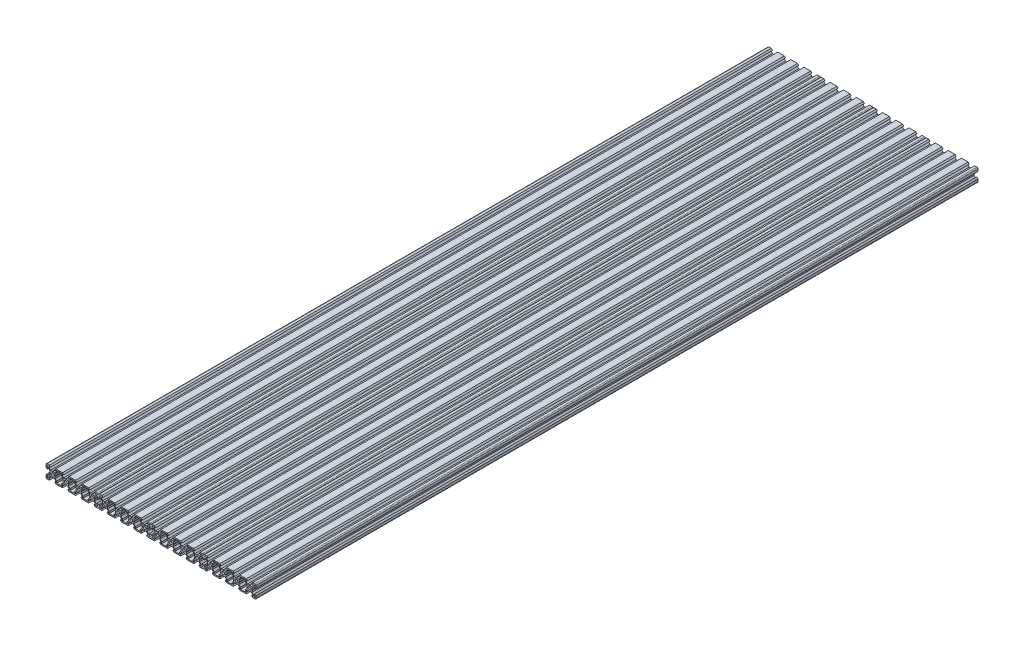
SolidWorks part; units mm, degrees
ref_plane "Front Plane" through (0, 0, 0) normal (0, 0, 1) x (1, 0, 0)
ref_plane "Top Plane" through (0, 0, 0) normal (0, 1, 0) x (1, 0, 0)
ref_plane "Right Plane" through (0, 0, 0) normal (1, 0, 0) x (0, 0, -1)
sketch "Sketch1" plane through (0, 0, 0) normal (0, 0, 1) x (1, 0, 0)
  line L0 (4.9, -10) -> (15.0977, -10)
  line L1 (-8.2011, 3.1) -> (-10.0011, 4.9)
  line L2 (-3.1, 8.2) -> (-5.4, 8.2)
  line L3 (-5.4, 8.2) -> (-5.4, 6.3)
  line L4 (-5.4, 6.3) -> (-3.1, 4)
  line L5 (-3.1, 4) -> (-0.5, 4)
  line L6 (3.1, 4) -> (5.4, 6.3)
  line L7 (5.4, 6.3) -> (5.4, 8.2)
  line L8 (5.4, 8.2) -> (3.1, 8.2)
  line L9 (-8.2135, -3.1) -> (-10.0011, -4.8876)
  line L10 (4.9, 10) -> (15.0977, 10)
  line L11 (0.5, 4) -> (3.1, 4)
  line L12 (5.4, -8.2) -> (3.1, -8.2)
  line L13 (5.4, -6.3) -> (5.4, -8.2)
  line L14 (3.1, -4) -> (5.4, -6.3)
  line L15 (-3.1, -4) -> (-0.5, -4)
  line L16 (-5.4, -6.3) -> (-3.1, -4)
  line L17 (-5.4, -8.2) -> (-5.4, -6.3)
  line L18 (-3.1, -8.2) -> (-5.4, -8.2)
  line L19 (-4.0135, 0.5) -> (-4.0135, 3.1)
  line L20 (-10.0011, -4.8876) -> (-10.0011, -8.5)
  line L21 (0.5, -4) -> (3.1, -4)
  line L22 (-8.2135, -3.1) -> (-8.2135, -5.4)
  line L23 (-8.2135, -5.4) -> (-6.3135, -5.4)
  line L24 (-6.3135, -5.4) -> (-4.0135, -3.1)
  line L25 (-4.0135, -3.1) -> (-4.0135, -0.5)
  line L26 (-4.0135, 3.1) -> (-6.3135, 5.4)
  line L27 (-6.3135, 5.4) -> (-8.2135, 5.4)
  line L28 (-8.2135, 5.4) -> (-8.2011, 3.1)
  line L29 (3.9989, 0.5) -> (3.9989, 3.1)
  line L30 (6.2989, 5.4) -> (6.2989, 8.2)
  line L31 (6.2989, -5.4) -> (6.2989, -8.2)
  line L32 (6.2989, -8.2) -> (13.6989, -8.2)
  line L33 (3.9989, 3.1) -> (6.2989, 5.4)
  line L34 (3.9989, -3.1) -> (3.9989, -0.5)
  line L35 (6.2989, -5.4) -> (3.9989, -3.1)
  line L36 (13.6989, -5.4) -> (13.6989, -8.2)
  line L37 (24.8977, 10) -> (35.1, 10)
  line L38 (24.8977, -10) -> (35.1, -10)
  line L39 (26.3113, -5.4) -> (26.3113, -8.2)
  line L40 (-10.0011, 8.5) -> (-10.0011, 4.9)
  line L41 (-8.5011, 10) -> (-4.9, 10)
  line L42 (-10.0011, 8.5) -> (-10.0011, 4.9)
  line L43 (-8.5011, -10) -> (-4.9, -10)
  line L44 (6.2989, 8.2) -> (13.6989, 8.2)
  line L45 (-8.2011, 7.0732) -> (-8.2011, 7.7)
  line L46 (-7.7011, 8.2) -> (-7.0738, 8.2)
  line L47 (-6.8971, 7.7732) -> (-7.7744, 6.8964)
  line L48 (-3.1, 8.2) -> (-4.9, 10)
  line L49 (3.1, 8.2) -> (4.9, 10)
  line L50 (-3.1, -8.2) -> (-4.9, -10)
  line L51 (3.1, -8.2) -> (4.9, -10)
  line L52 (36.9, 8.2) -> (34.6, 8.2)
  line L53 (34.6, 8.2) -> (34.6, 6.3)
  line L54 (13.6989, 8.2) -> (13.6989, 5.4)
  line L55 (34.6, 6.3) -> (36.9, 4)
  line L56 (36.9, 4) -> (39.5, 4)
  line L57 (43.1, 4) -> (45.4, 6.3)
  line L58 (45.4, 6.3) -> (45.4, 8.2)
  line L59 (45.4, 8.2) -> (43.1, 8.2)
  line L60 (-6.8971, -7.7732) -> (-7.7744, -6.8964)
  line L61 (-7.7011, -8.2) -> (-7.0738, -8.2)
  line L62 (-8.2011, -7.0732) -> (-8.2011, -7.7)
  line L63 (26.3113, -8.2) -> (33.6865, -8.2)
  line L64 (33.6865, -8.2) -> (33.6865, -5.4)
  line L65 (26.3113, 5.4) -> (26.3113, 8.2)
  line L66 (40.5, 4) -> (43.1, 4)
  line L67 (45.4, -8.2) -> (43.1, -8.2)
  line L68 (45.4, -6.3) -> (45.4, -8.2)
  line L69 (43.1, -4) -> (45.4, -6.3)
  line L70 (36.9, -4) -> (39.5, -4)
  line L71 (34.6, -6.3) -> (36.9, -4)
  line L72 (34.6, -8.2) -> (34.6, -6.3)
  line L73 (16.8977, -8.2) -> (15.0977, -10)
  line L74 (23.0977, -8.2) -> (24.8977, -10)
  line L75 (16.8977, 8.2) -> (15.0977, 10)
  line L76 (23.0977, 8.2) -> (24.8977, 10)
  line L77 (26.3113, 8.2) -> (33.6865, 8.2)
  line L78 (33.6865, 8.2) -> (33.6865, 5.4)
  line L84 (36.9, -8.2) -> (34.6, -8.2)
  line L85 (35.9865, 0.5) -> (35.9865, 3.1)
  line L86 (40.5, -4) -> (43.1, -4)
  line L87 (13.6989, -5.4) -> (15.9989, -3.1)
  line L88 (15.9989, -3.1) -> (15.9989, -0.5)
  line L89 (15.9989, 3.1) -> (13.6989, 5.4)
  line L92 (15.9989, 0.5) -> (15.9989, 3.1)
  line L95 (24.0113, 3.1) -> (26.3113, 5.4)
  line L96 (24.0113, -3.1) -> (24.0113, -0.5)
  line L97 (26.3113, -5.4) -> (24.0113, -3.1)
  line L100 (19.4977, -4) -> (16.8977, -4)
  line L102 (24.0113, 0.5) -> (24.0113, 3.1)
  line L103 (23.0977, -8.2) -> (25.3977, -8.2)
  line L104 (25.3977, -8.2) -> (25.3977, -6.3)
  line L105 (25.3977, -6.3) -> (23.0977, -4)
  line L106 (23.0977, -4) -> (20.4977, -4)
  line L107 (16.8977, -4) -> (14.5977, -6.3)
  line L108 (14.5977, -6.3) -> (14.5977, -8.2)
  line L109 (14.5977, -8.2) -> (16.8977, -8.2)
  line L110 (19.4977, 4) -> (16.8977, 4)
  line L111 (33.6865, -5.4) -> (35.9865, -3.1)
  line L113 (14.5977, 8.2) -> (16.8977, 8.2)
  line L114 (14.5977, 6.3) -> (14.5977, 8.2)
  line L115 (16.8977, 4) -> (14.5977, 6.3)
  line L116 (23.0977, 4) -> (20.4977, 4)
  line L117 (25.3977, 6.3) -> (23.0977, 4)
  line L118 (25.3977, 8.2) -> (25.3977, 6.3)
  line L119 (23.0977, 8.2) -> (25.3977, 8.2)
  line L121 (35.9865, -3.1) -> (35.9865, -0.5)
  line L122 (35.9865, 3.1) -> (33.6865, 5.4)
  line L125 (43.9989, 0.5) -> (43.9989, 3.1)
  line L126 (43.9989, 3.1) -> (46.2989, 5.4)
  line L127 (43.9989, -3.1) -> (43.9989, -0.5)
  line L128 (46.2989, -5.4) -> (43.9989, -3.1)
  line L134 (36.9, 8.2) -> (35.1, 10)
  line L135 (43.1, 8.2) -> (44.9, 10)
  line L136 (36.9, -8.2) -> (35.1, -10)
  line L137 (43.1, -8.2) -> (44.9, -10)
  line L140 (68.1989, -7.0732) -> (68.1989, -7.7)
  line L141 (67.6989, -8.2) -> (67.0716, -8.2)
  line L142 (66.8948, -7.7732) -> (67.7721, -6.8964)
  line L143 (46.2989, 8.2) -> (46.2989, 5.4)
  line L144 (56.8977, -8.2) -> (55.0977, -10)
  line L145 (63.0977, -8.2) -> (64.8977, -10)
  line L146 (56.8977, 8.2) -> (55.0977, 10)
  line L147 (63.0977, 8.2) -> (64.8977, 10)
  line L148 (66.8948, 7.7732) -> (67.7721, 6.8964)
  line L149 (67.6989, 8.2) -> (67.0716, 8.2)
  line L150 (68.1989, 7.0732) -> (68.1989, 7.7)
  line L151 (53.6989, 8.2) -> (46.2989, 8.2)
  line L152 (68.4989, -10) -> (64.8977, -10)
  line L153 (69.9989, 8.5) -> (69.9989, 4.9)
  line L154 (68.4989, 10) -> (64.8977, 10)
  line L155 (69.9989, 8.5) -> (69.9989, 4.9)
  line L157 (46.2989, -5.4) -> (46.2989, -8.2)
  line L158 (53.6989, -5.4) -> (55.9989, -3.1)
  line L159 (55.9989, -3.1) -> (55.9989, -0.5)
  line L160 (55.9989, 3.1) -> (53.6989, 5.4)
  line L161 (53.6989, -8.2) -> (46.2989, -8.2)
  line L162 (53.6989, -5.4) -> (53.6989, -8.2)
  line L163 (53.6989, 5.4) -> (53.6989, 8.2)
  line L164 (55.9989, 0.5) -> (55.9989, 3.1)
  line L165 (68.2113, 5.4) -> (68.1989, 3.1)
  line L166 (66.3113, 5.4) -> (68.2113, 5.4)
  line L167 (64.0113, 3.1) -> (66.3113, 5.4)
  line L168 (64.0113, -3.1) -> (64.0113, -0.5)
  line L169 (66.3113, -5.4) -> (64.0113, -3.1)
  line L170 (68.2113, -5.4) -> (66.3113, -5.4)
  line L171 (68.2113, -3.1) -> (68.2113, -5.4)
  line L172 (59.4977, -4) -> (56.8977, -4)
  line L173 (69.9989, -4.8876) -> (69.9989, -8.5)
  line L174 (64.0113, 0.5) -> (64.0113, 3.1)
  line L175 (63.0977, -8.2) -> (65.3977, -8.2)
  line L176 (65.3977, -8.2) -> (65.3977, -6.3)
  line L177 (65.3977, -6.3) -> (63.0977, -4)
  line L178 (63.0977, -4) -> (60.4977, -4)
  line L179 (56.8977, -4) -> (54.5977, -6.3)
  line L180 (54.5977, -6.3) -> (54.5977, -8.2)
  line L181 (54.5977, -8.2) -> (56.8977, -8.2)
  line L182 (59.4977, 4) -> (56.8977, 4)
  line L183 (55.0977, 10) -> (44.9, 10)
  line L184 (68.2113, -3.1) -> (69.9989, -4.8876)
  line L185 (54.5977, 8.2) -> (56.8977, 8.2)
  line L186 (54.5977, 6.3) -> (54.5977, 8.2)
  line L187 (56.8977, 4) -> (54.5977, 6.3)
  line L188 (63.0977, 4) -> (60.4977, 4)
  line L189 (65.3977, 6.3) -> (63.0977, 4)
  line L190 (65.3977, 8.2) -> (65.3977, 6.3)
  line L191 (63.0977, 8.2) -> (65.3977, 8.2)
  line L192 (68.1989, 3.1) -> (69.9989, 4.9)
  line L193 (55.0977, -10) -> (44.9, -10)
  circle A0 centre (0, 0) radius 2.1
  arc A1 (-10.0011, -8.5) -> (-8.5011, -10) centre (-8.5011, -8.5) ccw
  arc A2 (0.5, -4) -> (-0.5, -4) centre (0, -4) ccw
  arc A3 (20.4977, -4) -> (19.4977, -4) centre (19.9977, -4) ccw
  arc A4 (-8.5011, 10) -> (-10.0011, 8.5) centre (-8.5011, 8.5) ccw
  arc A5 (-8.2011, 7.7) -> (-7.7011, 8.2) centre (-7.7011, 7.7) cw
  arc A6 (-7.0738, 8.2) -> (-6.8971, 7.7732) centre (-7.0738, 7.95) cw
  arc A7 (-8.2011, 7.0732) -> (-7.7744, 6.8964) centre (-7.9511, 7.0732) ccw
  arc A8 (-0.5, 4) -> (0.5, 4) centre (0, 4) ccw
  circle A9 centre (40, 0) radius 2.1
  arc A10 (-4.0135, -0.5) -> (-4.0135, 0.5) centre (-4.0135, 0) ccw
  arc A11 (3.9989, 0.5) -> (3.9989, -0.5) centre (3.9989, 0) ccw
  arc A17 (39.5, 4) -> (40.5, 4) centre (40, 4) ccw
  arc A18 (-8.2011, -7.0732) -> (-7.7744, -6.8964) centre (-7.9511, -7.0732) cw
  arc A19 (-7.0738, -8.2) -> (-6.8971, -7.7732) centre (-7.0738, -7.95) ccw
  arc A20 (-8.2011, -7.7) -> (-7.7011, -8.2) centre (-7.7011, -7.7) ccw
  arc A24 (35.9865, -0.5) -> (35.9865, 0.5) centre (35.9865, 0) ccw
  arc A25 (43.9989, 0.5) -> (43.9989, -0.5) centre (43.9989, 0) ccw
  arc A29 (68.1989, -7.7) -> (67.6989, -8.2) centre (67.6989, -7.7) cw
  arc A30 (15.9989, 0.5) -> (15.9989, -0.5) centre (15.9989, 0) cw
  arc A31 (24.0113, -0.5) -> (24.0113, 0.5) centre (24.0113, 0) cw
  arc A32 (67.0716, -8.2) -> (66.8948, -7.7732) centre (67.0716, -7.95) cw
  arc A33 (20.4977, 4) -> (19.4977, 4) centre (19.9977, 4) cw
  arc A38 (68.1989, -7.0732) -> (67.7721, -6.8964) centre (67.9489, -7.0732) ccw
  arc A39 (55.9989, 0.5) -> (55.9989, -0.5) centre (55.9989, 0) cw
  circle A41 centre (19.9977, 0) radius 2.1
  arc A42 (64.0113, -0.5) -> (64.0113, 0.5) centre (64.0113, 0) cw
  arc A43 (60.4977, 4) -> (59.4977, 4) centre (59.9977, 4) cw
  arc A44 (68.1989, 7.0732) -> (67.7721, 6.8964) centre (67.9489, 7.0732) cw
  arc A45 (67.0716, 8.2) -> (66.8948, 7.7732) centre (67.0716, 7.95) ccw
  arc A46 (68.1989, 7.7) -> (67.6989, 8.2) centre (67.6989, 7.7) ccw
  arc A47 (68.4989, 10) -> (69.9989, 8.5) centre (68.4989, 8.5) cw
  arc A48 (39.5, -4) -> (40.5, -4) centre (40, -4) cw
  arc A49 (59.4977, -4) -> (60.4977, -4) centre (59.9977, -4) cw
  arc A50 (69.9989, -8.5) -> (68.4989, -10) centre (68.4989, -8.5) cw
  circle A51 centre (59.9977, 0) radius 2.1
extrude "Boss-Extrude1" add sketch "Sketch1" along normal blind 1100 contours A50 L173 L184 L171 L170 L169 L168 A42 L174 L167 L166 L165 L192 L153 A47 L154 L147 L191 L190 L189 L188 A43 L182 L187 L186 L185 L146 L183 L135 L59 L58 L57 L66 A17 L56 L55 L53 L52 L134 L37 L76 L119 L118 L117 L116 A33 L110 L115 L114 L113 L75
ref_plane "Plane1" through (-10, 0, 0) normal (1, 0, 0) x (0, 0, -1)
mirror "Mirror1" about plane through (-10, 0, 0) normal (1, 0, 0) of "Boss-Extrude1"
mirror "Mirror3" about plane through (-89.9989, 0, 1100) normal (1, 0, 0) of "Mirror1", "Boss-Extrude1"
